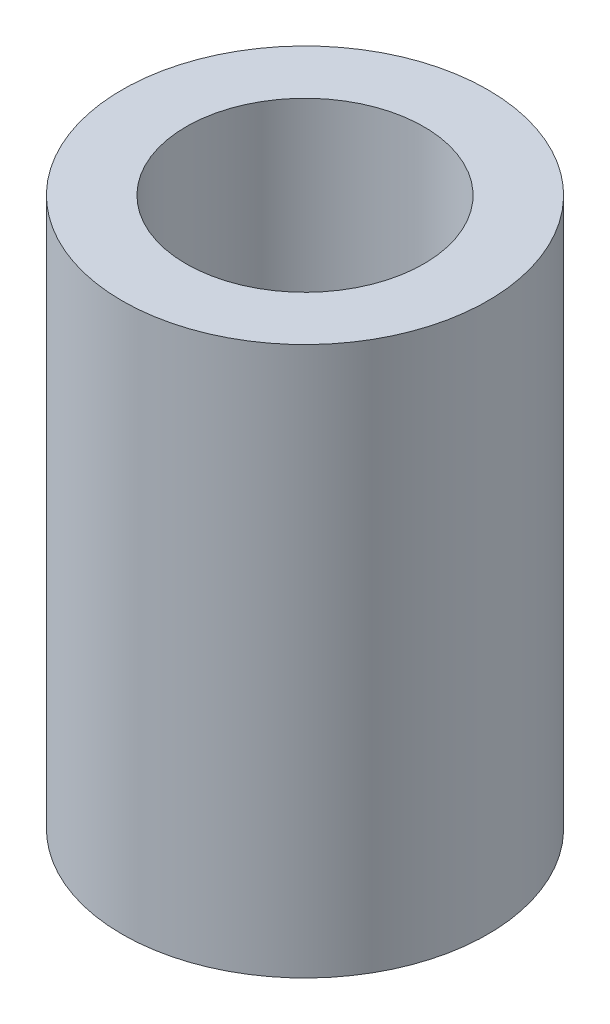
SolidWorks part; units mm, degrees
ref_plane "Front Plane" through (0, 0, 0) normal (0, 0, 1) x (1, 0, 0)
ref_plane "Top Plane" through (0, 0, 0) normal (0, 1, 0) x (1, 0, 0)
ref_plane "Right Plane" through (0, 0, 0) normal (1, 0, 0) x (0, 0, -1)
sketch "Sketch1" plane through (0, 0, 0) normal (0, 1, 0) x (1, 0, 0)
  circle A0 centre (0, 0) radius 3.25
  circle A1 centre (0, 0) radius 5
  dimension "D1" = 6.5
  dimension "D2" = 10
extrude "Boss-Extrude1" add sketch "Sketch1" along normal blind 15
